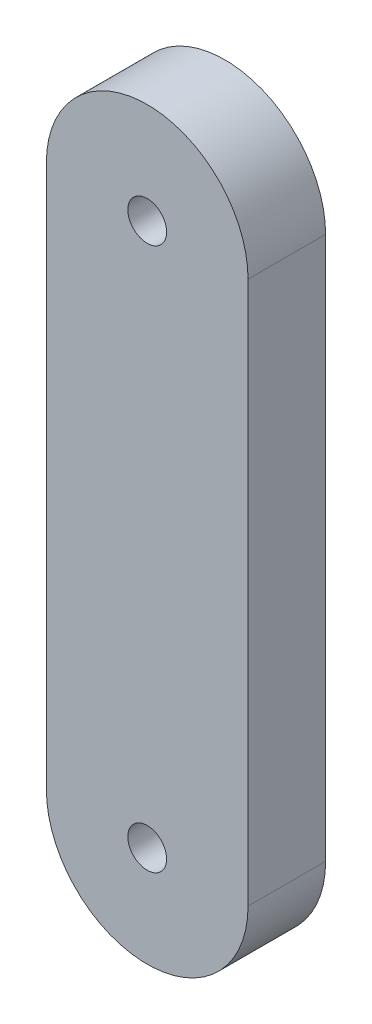
SolidWorks part; units mm, degrees
ref_plane "Front Plane" through (0, 0, 0) normal (0, 0, 1) x (1, 0, 0)
ref_plane "Top Plane" through (0, 0, 0) normal (0, 1, 0) x (1, 0, 0)
ref_plane "Right Plane" through (0, 0, 0) normal (1, 0, 0) x (0, 0, -1)
sketch "Sketch1" plane through (0, 0, 0) normal (0, 0, 1) x (1, 0, 0)
  line L0 (0, 0) -> (0, 17.5) construction
  line L1 (-3.25, 0) -> (-3.25, 17.5)
  line L2 (3.25, 0) -> (3.25, 17.5)
  arc A0 (-3.25, 0) -> (3.25, 0) centre (0, 0) ccw
  arc A1 (3.25, 17.5) -> (-3.25, 17.5) centre (0, 17.5) ccw
  circle A2 centre (0, 17.5) radius 0.625
  circle A3 centre (0, 0) radius 0.625
  point P2 (0, 8.75)
  point P11 (0, 0)
  dimension "D2" = 3.25
  dimension "D3" = 1.25
  dimension "D1" = 17.5
extrude "Boss-Extrude1" add sketch "Sketch1" along normal blind 2.5
